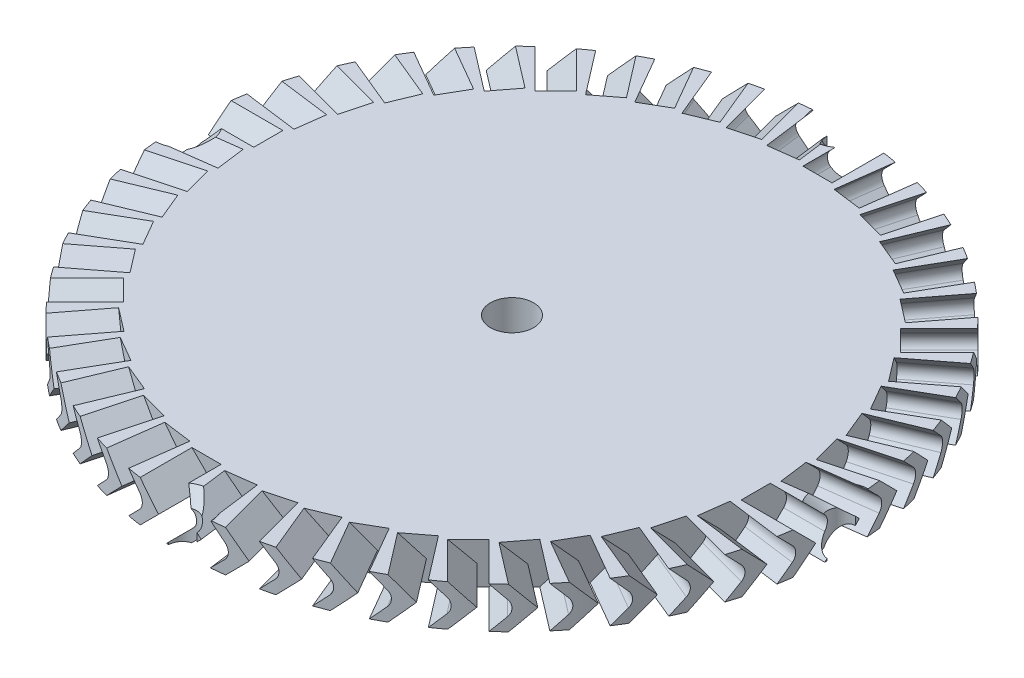
SolidWorks part; units mm, degrees
material "AISI 316 Annealed Stainless Steel Bar (SS)"
ref_plane "Front Plane" through (0, 0, 0) normal (0, 0, 1) x (1, 0, 0)
ref_plane "Top Plane" through (0, 0, 0) normal (0, 1, 0) x (1, 0, 0)
ref_plane "Right Plane" through (0, 0, 0) normal (1, 0, 0) x (0, 0, -1)
sketch "Sketch1" plane through (0, 0, 0) normal (0, 1, 0) x (1, 0, 0)
  circle A0 centre (0, 0) radius 5
  circle A1 centre (0, 0) radius 76.2
  point P15 (0, 0)
  dimension "D1" = 10
  dimension "D2" = 152.4
extrude "Boss-Extrude1" add sketch "Sketch1" along normal blind 9.525
ref_plane "Plane1" through (0, 0, 76.2) normal (0, 0, 1) x (1, 0, 0)
sketch "Sketch2" plane through (0, 0, 76.2) normal (0, 0, 1) x (1, 0, 0)
  line L4 (-0.6975, 3.0787) -> (-3.7762, 0)
  line L5 (-76.2, 0) -> (76.2, 0) construction
  line L6 (-0.6975, 6.4463) -> (-3.7762, 9.525)
  line L9 (76.2, 9.525) -> (-76.2, 9.525) construction
  line L10 (-4.065, 3.0787) -> (-10.5113, 9.525)
  line L11 (-4.065, 6.4463) -> (-10.5113, 0)
  line L12 (-10.5113, 9.525) -> (-3.7762, 9.525)
  line L13 (-10.5113, 0) -> (-3.7762, 0)
  line L14 (0, 0) -> (0, 9.525) construction
  line L15 (5, 9.525) -> (-5, 9.525) construction
  line L16 (-2.3813, 4.7625) -> (0, 4.7625) construction
  circle A0 centre (-2.3813, 4.7625) radius 2.3813
  point P19 (0, 4.7625)
  dimension "D1" = 4.7625
  dimension "D2" = 45
  dimension "D3" = 45
extrude "Blade Gaps" cut sketch "Sketch2" against normal blind 12.7 contours A0 | A0 L6 L12 L10 L11 | A0 L11 L10 | A0 L10 L11 L13 L4 region at (-5.8607, 1.718, 76.2) region at (-2.3813, 4.7625, 76.2) region at (-4.9966, 4.7625, 76.2) region at (-5.8607, 7.807, 76.2)
pattern_circular "CirPattern1" count 48 over 360 about axis through (0, 9.525, 0) along (0, -1, 0) of "Blade Gaps" reverse direction yes
hole_wizard "CSK for 1/4 Flat Head Machine Screw (100)1" positions "3DSketch1" profile "Sketch3" countersink size "1/4" standard "ANSI Inch"
sketch3d "3DSketch1"
  line L0 (0, 0, 0) -> (0, 0, 76.2) construction
  point P0 (0, 9.525, 76.2)
sketch "Sketch3" plane through (0, 9.525, 76.2) normal (1, 0, 0) x (0, 0, 1)
  line L0 (0, 0) -> (0, 14.6611)
  line L1 (0, 14.6611) -> (3.2639, 12.7)
  line L2 (3.2639, 12.7) -> (3.2639, 2.6641)
  line L3 (3.2639, 2.6641) -> (6.4389, 0)
  line L5 (6.4389, 0) -> (0, 0)
  line L6 (-3.2639, 2.6641) -> (-6.4389, 0) construction
  line L10 (0, 14.6611) -> (-3.2639, 12.7) construction
  line L11 (0, -6.35) -> (0, 107.95) construction
  dimension "Hole Dia." = 6.5278
  dimension "Hole Depth" = 12.7
  dimension "Near C'Sink Dia." = 12.8778
  dimension "Near C'Sink Angle" = 100
  dimension "Drill Angle" = 118
pattern_circular "CirPattern2" count 4 over 360 about axis through (0, 9.525, 0) along (0, -1, 0) of "CSK for 1/4 Flat Head Machine Screw (100)1" reverse direction yes
